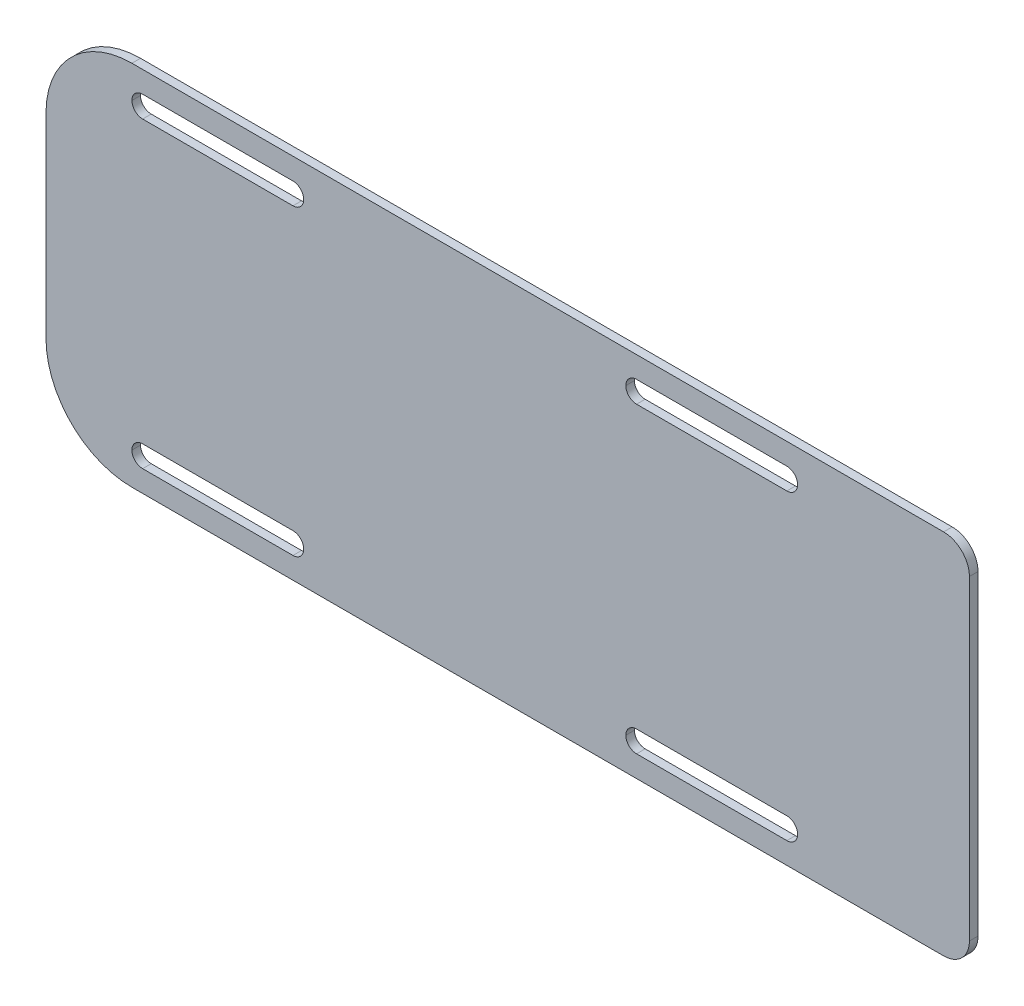
SolidWorks part; units mm, degrees
ref_plane "Plan de face" through (0, 0, 0) normal (0, 0, 1) x (1, 0, 0)
ref_plane "Plan de dessus" through (0, 0, 0) normal (0, 1, 0) x (1, 0, 0)
ref_plane "Plan de droite" through (0, 0, 0) normal (1, 0, 0) x (0, 0, -1)
sketch "Esquisse1" plane through (0, 0, 0) normal (0, 0, 1) x (1, 0, 0)
  line L1 (0, 0) -> (215, 0)
  line L2 (0, 0) -> (0, 85.5)
  line L3 (0, 85.5) -> (215, 85.5)
  line L4 (215, 0) -> (215, 85.5)
  line L5 (175, 5) -> (135, 5)
  line L6 (175, 5) -> (175, 10)
  line L7 (175, 10) -> (135, 10)
  line L8 (135, 5) -> (135, 10)
  line L9 (175, 75.5) -> (135, 75.5)
  line L10 (175, 75.5) -> (175, 80.5)
  line L11 (175, 80.5) -> (135, 80.5)
  line L12 (135, 75.5) -> (135, 80.5)
  line L13 (60, 5) -> (20, 5)
  line L14 (60, 5) -> (60, 10)
  line L15 (60, 10) -> (20, 10)
  line L16 (20, 5) -> (20, 10)
  line L17 (60, 75.5) -> (20, 75.5)
  line L18 (60, 75.5) -> (60, 80.5)
  line L19 (60, 80.5) -> (20, 80.5)
  line L20 (20, 75.5) -> (20, 80.5)
  dimension "D1" = 215
  dimension "D2" = 85.5
  dimension "D3" = 5
  dimension "D4" = 5
  dimension "D5" = 5
  dimension "D6" = 5
  dimension "D7" = 40
  dimension "D8" = 40
  dimension "D9" = 40
  dimension "D10" = 40
  dimension "D11" = 5
  dimension "D12" = 5
  dimension "D13" = 20
  dimension "D14" = 20
  dimension "D15" = 40
  dimension "D16" = 40
  dimension "D17" = 5
  dimension "D18" = 5
extrude "Boss.-Extru.1" add sketch "Esquisse1" along normal blind 2
fillet "Congé1" radius 6 2 edges at (215, 0, 1) (215, 85.5, 1)
fillet "Congé2" radius 20 2 edges at (0, 0, 1) (0, 85.5, 1)
fillet "Congé3" radius 2.5 16 edges at (20, 80.5, 1) (20, 75.5, 1) (60, 75.5, 1) (60, 80.5, 1) (60, 10, 1) (60, 5, 1) (20, 5, 1) (20, 10, 1) (135, 10, 1) (135, 5, 1) (175, 10, 1) (175, 5, 1) (135, 80.5, 1) (135, 75.5, 1) (175, 75.5, 1) (175, 80.5, 1)
